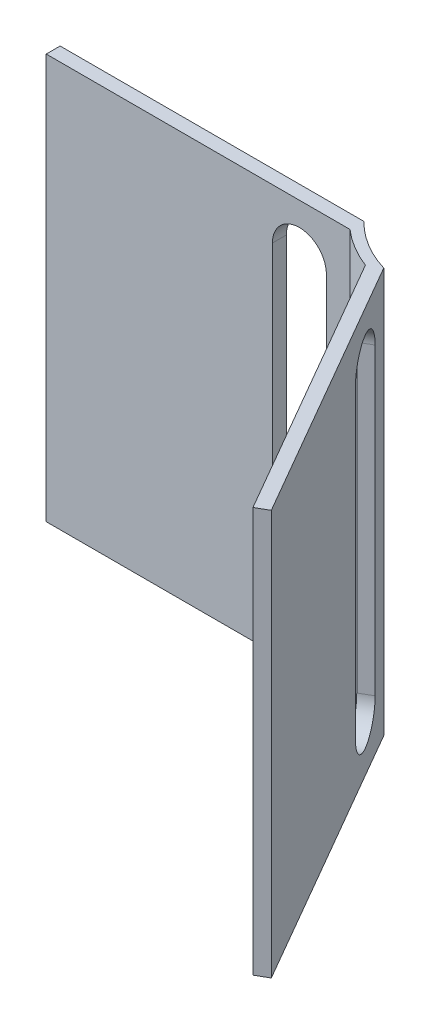
SolidWorks part; units mm, degrees
ref_plane "Plan de face" through (0, 0, 0) normal (0, 0, 1) x (1, 0, 0)
ref_plane "Plan de dessus" through (0, 0, 0) normal (0, 1, 0) x (1, 0, 0)
ref_plane "Plan de droite" through (0, 0, 0) normal (1, 0, 0) x (0, 0, -1)
sketch "Esquisse3" plane through (0, 0, 0) normal (0, 1, 0) x (1, 0, 0)
  line L0 (-150.1573, 0) -> (189.6273, 0) construction
  line L1 (-83.8395, -145.9242) -> (87.7229, 151.2306) construction
  line L2 (-78.0725, 135.2255) -> (117.7517, -203.9519) construction
  line L3 (-125, 131.2995) -> (-125, -153.5705) construction
  line L4 (-25, -24.4949) -> (-115, -24.4949)
  line L6 (-21.2883, 25.5051) -> (-23.9685, 25.5051)
  line L7 (-115, -24.4949) -> (-115, 25.5051)
  line L8 (-25, -24.4949) -> (-115, 25.5051) construction
  line L9 (-21.2883, 25.5051) -> (-115, -24.4949) construction
  line L10 (-23.9685, 25.5051) -> (-115, 25.5051)
  line L11 (34.0723, 8.0048) -> (79.5881, 86.8404)
  line L12 (36.2868, 111.8404) -> (79.5881, 86.8404)
  line L13 (-8.7132, 33.8981) -> (36.2868, 111.8404)
  line L14 (-10.1038, -33.5099) -> (35.4119, -112.3455)
  line L15 (78.7132, -87.3455) -> (35.4119, -112.3455)
  line L16 (33.7132, -9.4032) -> (78.7132, -87.3455)
  line L17 (-23.9685, 25.5051) -> (-25, -24.4949)
  line L18 (-8.7132, 33.8981) -> (34.0723, 8.0048)
  line L19 (-10.1038, -33.5099) -> (33.7132, -9.4032)
  line L20 (-25, -28.6182) -> (-115, -28.6182)
  line L21 (-115, -28.6182) -> (-115, -24.4949)
  line L22 (-13.5526, -35.5011) -> (31.9631, -114.3367)
  line L23 (31.9631, -114.3367) -> (35.4119, -112.3455)
  circle A0 centre (0, 0) radius 125
  circle A1 centre (0, 0) radius 35
  circle A2 centre (0, 0) radius 125
  circle A3 centre (0, 0) radius 125
  circle A4 centre (0, 0) radius 38
  point P9 (-69.0908, 0)
  point P32 (0, 0)
  dimension "D1" = 250
  dimension "D4" = 70
  dimension "D2" = 120
  dimension "D3" = 120
  dimension "D5" = 10
  dimension "D6" = 50
  dimension "D7" = 90
  dimension "D9" = 3
  dimension "D8" = 3
extrude "Boss.-Extru.1" add sketch "Esquisse3" along normal blind 120 contours A4 L4 L21 L20 | L4 A4 L14 A1 | A4 L22 L23 L14 region at (-18.6168, 0, 30.8794) region at (-71.0566, 0, 26.5723) region at (11.4638, 0, 74.8797)
sketch "Esquisse4" plane through (0, 0, 28.6182) normal (0, 0, 1) x (1, 0, 0)
  line L0 (-40, 120) -> (-40, 0) construction
  line L1 (-25, 120) -> (-115, 120) construction
  line L2 (-25, 0) -> (-115, 0) construction
  line L3 (-48, 105) -> (-48, 15)
  line L4 (-25, 120) -> (-25, 0) construction
  line L5 (-115, 60) -> (-20.315, 60) construction
  line L6 (-115, 120) -> (-115, 0) construction
  line L7 (-32, 105) -> (-32, 15)
  arc A0 (-48, 15) -> (-32, 15) centre (-40, 15) ccw
  arc A1 (-48, 105) -> (-32, 105) centre (-40, 105) cw
  point P12 (-40, 105.1536)
  dimension "D1" = 8
  dimension "D2" = 15
  dimension "D3" = 45
  dimension "D4" = 45
extrude "Enlèv. mat.-Extru.1" cut sketch "Esquisse4" against normal through all
sketch "Esquisse5" plane through (-25.5369, 0, 14.7437) normal (-0.866, 0, 0.5) x (0.5, 0, 0.866)
  line L0 (38.9685, 120) -> (38.9685, 0) construction
  line L1 (23.9685, 120) -> (115, 120) construction
  line L2 (46.9685, 105) -> (46.9685, 15)
  line L3 (38.9685, 60) -> (127.8483, 60) construction
  line L4 (115, 120) -> (115, 0) construction
  line L5 (23.9685, 120) -> (23.9685, 0) construction
  line L6 (30.9685, 105) -> (30.9685, 15)
  arc A0 (46.9685, 15) -> (30.9685, 15) centre (38.9685, 15) cw
  arc A1 (46.9685, 105) -> (30.9685, 105) centre (38.9685, 105) ccw
  point P7 (38.9685, 101.0862)
  point P14 (115, 60)
  dimension "D1" = 8
  dimension "D2" = 45
  dimension "D3" = 45
  dimension "D4" = 15
extrude "Enlèv. mat.-Extru.2" cut sketch "Esquisse5" against normal through all
